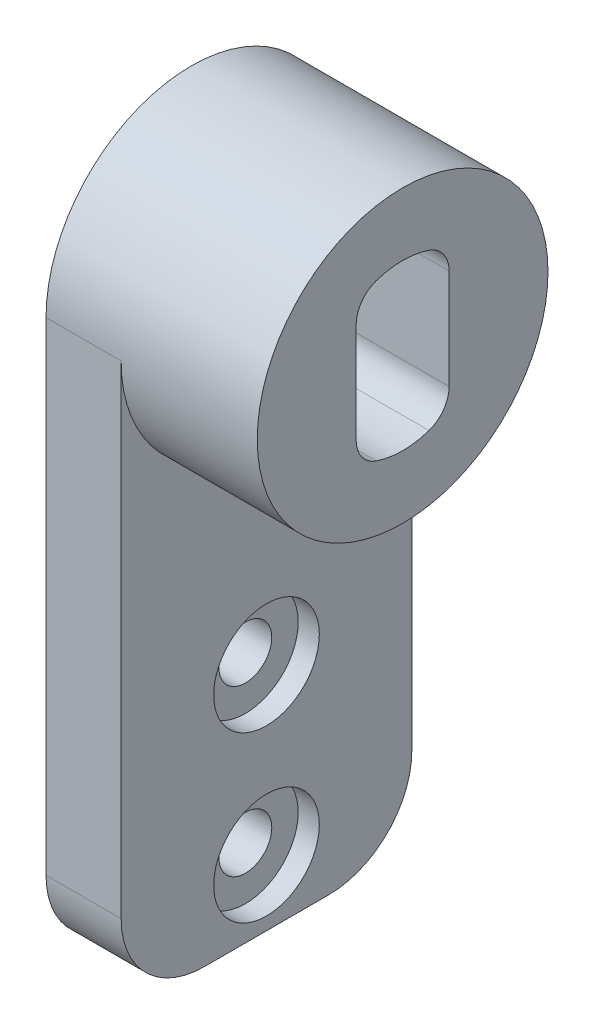
SolidWorks part; units mm, degrees
material "ABS"
ref_plane "Front Plane" through (0, 0, 0) normal (1, 0, 0) x (0, 1, 0)
ref_plane "Top Plane" through (0, 0, 0) normal (0, 0, 1) x (0, 1, 0)
ref_plane "Right Plane" through (0, 0, 0) normal (0, 1, 0) x (-1, 0, 0)
sketch "Sketch1" plane through (0, 0, 0) normal (1, 0, 0) x (0, 1, 0)
  circle A2 centre (0, 0) radius 8.7376
  dimension "D3" = 17.4752
extrude "Boss-Extrude1" add sketch "Sketch1" along normal blind 12.7 contours A2 region at (0, 0, 0)
sketch "Sketch10" plane through (0, 0, 0) normal (-1, 0, 0) x (0, -1, 0)
  line L0 (0, 8.7376) -> (34.036, 8.7376)
  line L2 (34.036, 8.7376) -> (34.036, -8.7376)
  line L3 (34.036, -8.7376) -> (0, -8.7376)
  circle A0 centre (0, 0) radius 8.7376 construction
  arc A2 (0, 8.7376) -> (0, -8.7376) centre (0, 0) cw
  dimension "D1" = 34.036
extrude "Boss-Extrude3" add sketch "Sketch10" against normal blind 4.516 contours L0 A2 L3 L2 region at (0, -20.3793, 0)
fillet "Fillet2" radius 5 2 edges at (2.258, -34.036, 8.7376) (2.258, -34.036, -8.7376)
sketch "Sketch14" [suppressed] plane through (0, 0, 0) normal (-1, 0, 0) x (0, 0, 1)
  line L0 (0.5115, -3.4237) -> (0.3944, -4.0089)
  line L1 (0, 0) -> (0, -4.064) construction
  line L2 (0, 0) -> (0.5606, -3.4335) construction
  line L3 (0.6039, -3.4087) -> (0.9011, -3.9262)
  line L4 (-0.6903, -3.3922) -> (-1.0005, -3.9021)
  line L5 (-0.5983, -3.4096) -> (-0.4961, -3.9976)
  line L6 (-1.8089, -2.9515) -> (-2.2748, -3.3245)
  line L7 (-1.7284, -2.9994) -> (-1.8334, -3.5869)
  line L8 (-2.7093, -2.1549) -> (-3.2746, -2.346)
  line L9 (-2.65, -2.2273) -> (-2.9496, -2.7435)
  line L10 (-3.2829, -1.0983) -> (-3.8795, -1.0846)
  line L11 (-3.252, -1.1867) -> (-3.7101, -1.5692)
  line L12 (-3.4605, 0.0907) -> (-4.0165, 0.3077)
  line L13 (-3.4617, -0.0029) -> (-4.023, -0.2057)
  line L14 (-3.2208, 1.2689) -> (-3.669, 1.6629)
  line L15 (-3.2539, 1.1813) -> (-3.8507, 1.1827)
  line L16 (-2.5926, 2.2939) -> (-2.879, 2.8175)
  line L17 (-2.6537, 2.223) -> (-3.214, 2.4284)
  line L18 (-1.6517, 3.0423) -> (-1.7417, 3.6323)
  line L19 (-1.7333, 2.9965) -> (-2.1896, 3.3812)
  line L20 (-0.5115, 3.4237) -> (-0.3944, 4.0089)
  line L21 (-0.6039, 3.4087) -> (-0.9011, 3.9262)
  line L22 (0.6903, 3.3922) -> (1.0005, 3.9021)
  line L23 (0.5983, 3.4096) -> (0.4961, 3.9976)
  line L24 (1.8089, 2.9515) -> (2.2748, 3.3245)
  line L25 (1.7284, 2.9994) -> (1.8334, 3.5869)
  line L26 (2.7093, 2.1549) -> (3.2746, 2.346)
  line L27 (2.65, 2.2273) -> (2.9496, 2.7435)
  line L28 (3.2829, 1.0983) -> (3.8795, 1.0846)
  line L29 (3.252, 1.1867) -> (3.7101, 1.5692)
  line L30 (3.4605, -0.0907) -> (4.0165, -0.3077)
  line L31 (3.4617, 0.0029) -> (4.023, 0.2057)
  line L32 (3.2208, -1.2689) -> (3.669, -1.6629)
  line L33 (3.2539, -1.1813) -> (3.8507, -1.1827)
  line L34 (2.5926, -2.2939) -> (2.879, -2.8175)
  line L35 (2.6537, -2.223) -> (3.214, -2.4284)
  line L36 (1.6517, -3.0423) -> (1.7417, -3.6323)
  line L37 (1.7333, -2.9965) -> (2.1896, -3.3812)
  line L38 (-0.1032, -4.0627) -> (0, -4.064)
  line L39 (-1.4865, -3.7824) -> (-1.39, -3.8189)
  line L40 (-2.6905, -3.0459) -> (-2.6123, -3.1132)
  line L41 (-3.5195, -2.032) -> (-3.57, -1.942)
  line L42 (-4.0023, -0.7057) -> (-4.0189, -0.6039)
  line L43 (-4.0023, 0.7057) -> (-3.9831, 0.8071)
  line L44 (-3.5195, 2.032) -> (-3.4668, 2.1207)
  line L45 (-2.6123, 3.1132) -> (-2.5324, 3.1785)
  line L46 (-1.39, 3.8189) -> (-1.2926, 3.853)
  line L47 (0, 4.064) -> (0.1032, 4.0627)
  line L48 (1.39, 3.8189) -> (1.4865, 3.7824)
  line L49 (2.6123, 3.1132) -> (2.6905, 3.0459)
  line L50 (3.5195, 2.032) -> (3.57, 1.942)
  line L51 (4.0023, 0.7057) -> (4.0189, 0.6039)
  line L52 (4.0023, -0.7057) -> (3.9831, -0.8071)
  line L53 (3.5195, -2.032) -> (3.4668, -2.1207)
  line L54 (2.6123, -3.1132) -> (2.5324, -3.1785)
  line L55 (1.39, -3.8189) -> (1.2926, -3.853)
  arc A0 (0.3497, -4.0489) -> (0, -4.064) centre (0, 0) cw
  arc A1 (0.3497, -4.0489) -> (0.3944, -4.0089) centre (0.3454, -3.9991) ccw
  arc A2 (0.5115, -3.4237) -> (0.6039, -3.4087) centre (0.5606, -3.4335) cw
  arc A3 (0.4203, -4.0631) -> (0.3944, -4.0089) centre (0.4434, -4.0187) cw
  arc A4 (0.4203, -4.0631) -> (0.7372, -4.2116) centre (2.3016, -0.4608) ccw
  arc A6 (0.9562, -3.9499) -> (0.9011, -3.9262) centre (0.9445, -3.9013) cw
  arc A7 (0.9562, -3.9499) -> (1.2926, -3.853) centre (0, 0) ccw
  arc A8 (-1.0562, -3.9243) -> (-1.39, -3.8189) centre (0, 0) cw
  arc A9 (-1.0562, -3.9243) -> (-1.0005, -3.9021) centre (-1.0432, -3.8761) ccw
  arc A10 (-0.6903, -3.3922) -> (-0.5983, -3.4096) centre (-0.6476, -3.4182) cw
  arc A11 (-0.4524, -4.0387) -> (-0.4961, -3.9976) centre (-0.4468, -3.9891) cw
  arc A12 (-0.4524, -4.0387) -> (-0.1032, -4.0627) centre (0, 0) ccw
  arc A13 (-2.3347, -3.3264) -> (-2.6123, -3.1132) centre (0, 0) cw
  arc A14 (-2.3347, -3.3264) -> (-2.2748, -3.3245) centre (-2.306, -3.2855) ccw
  arc A15 (-1.8089, -2.9515) -> (-1.7284, -2.9994) centre (-1.7776, -2.9906) cw
  arc A16 (-1.8064, -3.6405) -> (-1.8334, -3.5869) centre (-1.7842, -3.5957) cw
  arc A17 (-1.8064, -3.6405) -> (-1.4865, -3.7824) centre (0, 0) ccw
  arc A18 (-3.3316, -2.3273) -> (-3.5195, -2.032) centre (0, 0) cw
  arc A19 (-3.3316, -2.3273) -> (-3.2746, -2.346) centre (-3.2906, -2.2987) ccw
  arc A20 (-2.7093, -2.1549) -> (-2.65, -2.2273) centre (-2.6933, -2.2022) cw
  arc A21 (-2.9426, -2.8031) -> (-2.9496, -2.7435) centre (-2.9064, -2.7686) cw
  arc A22 (-2.9426, -2.8031) -> (-2.6905, -3.0459) centre (0, 0) ccw
  arc A23 (-3.9267, -1.0475) -> (-4.0023, -0.7057) centre (0, 0) cw
  arc A24 (-3.9267, -1.0475) -> (-3.8795, -1.0846) centre (-3.8784, -1.0346) ccw
  arc A25 (-3.2829, -1.0983) -> (-3.252, -1.1867) centre (-3.284, -1.1483) cw
  arc A26 (-3.7238, -1.6276) -> (-3.7101, -1.5692) centre (-3.678, -1.6076) cw
  arc A27 (-3.7238, -1.6276) -> (-3.57, -1.942) centre (0, 0) ccw
  arc A28 (-4.0481, 0.3587) -> (-4.0023, 0.7057) centre (0, 0) cw
  arc A29 (-4.0481, 0.3587) -> (-4.0165, 0.3077) centre (-3.9983, 0.3543) ccw
  arc A30 (-3.4605, 0.0907) -> (-3.4617, -0.0029) centre (-3.4787, 0.0442) cw
  arc A31 (-4.0559, -0.2558) -> (-4.023, -0.2057) centre (-4.006, -0.2527) cw
  arc A32 (-4.0559, -0.2558) -> (-4.0189, -0.6039) centre (0, 0) ccw
  arc A33 (-3.6813, 1.7216) -> (-3.5195, 2.032) centre (0, 0) cw
  arc A34 (-3.6813, 1.7216) -> (-3.669, 1.6629) centre (-3.636, 1.7005) ccw
  arc A35 (-3.2208, 1.2689) -> (-3.2539, 1.1813) centre (-3.2538, 1.2313) cw
  arc A36 (-3.8988, 1.1468) -> (-3.8507, 1.1827) centre (-3.8509, 1.1327) cw
  arc A37 (-3.8988, 1.1468) -> (-3.9831, 0.8071) centre (0, 0) ccw
  arc A38 (-2.8705, 2.8769) -> (-2.6123, 3.1132) centre (0, 0) cw
  arc A39 (-2.8705, 2.8769) -> (-2.879, 2.8175) centre (-2.8352, 2.8415) ccw
  arc A40 (-2.5926, 2.2939) -> (-2.6537, 2.223) centre (-2.6365, 2.2699) cw
  arc A41 (-3.2715, 2.4111) -> (-3.214, 2.4284) centre (-3.2312, 2.3815) cw
  arc A42 (-3.2715, 2.4111) -> (-3.4668, 2.1207) centre (0, 0) ccw
  arc A43 (-1.7134, 3.6852) -> (-1.39, 3.8189) centre (0, 0) cw
  arc A44 (-1.7134, 3.6852) -> (-1.7417, 3.6323) centre (-1.6923, 3.6398) ccw
  arc A45 (-1.6517, 3.0423) -> (-1.7333, 2.9965) centre (-1.7011, 3.0348) cw
  arc A46 (-2.2495, 3.3846) -> (-2.1896, 3.3812) centre (-2.2218, 3.343) cw
  arc A47 (-2.2495, 3.3846) -> (-2.5324, 3.1785) centre (0, 0) ccw
  arc A48 (-0.3497, 4.0489) -> (0, 4.064) centre (0, 0) cw
  arc A49 (-0.3497, 4.0489) -> (-0.3944, 4.0089) centre (-0.3454, 3.9991) ccw
  arc A50 (-0.5115, 3.4237) -> (-0.6039, 3.4087) centre (-0.5606, 3.4335) cw
  arc A51 (-0.9562, 3.9499) -> (-0.9011, 3.9262) centre (-0.9445, 3.9013) cw
  arc A52 (-0.9562, 3.9499) -> (-1.2926, 3.853) centre (0, 0) ccw
  arc A53 (1.0562, 3.9243) -> (1.39, 3.8189) centre (0, 0) cw
  arc A54 (1.0562, 3.9243) -> (1.0005, 3.9021) centre (1.0432, 3.8761) ccw
  arc A55 (0.6903, 3.3922) -> (0.5983, 3.4096) centre (0.6476, 3.4182) cw
  arc A56 (0.4524, 4.0387) -> (0.4961, 3.9976) centre (0.4468, 3.9891) cw
  arc A57 (0.4524, 4.0387) -> (0.1032, 4.0627) centre (0, 0) ccw
  arc A58 (2.3347, 3.3264) -> (2.6123, 3.1132) centre (0, 0) cw
  arc A59 (2.3347, 3.3264) -> (2.2748, 3.3245) centre (2.306, 3.2855) ccw
  arc A60 (1.8089, 2.9515) -> (1.7284, 2.9994) centre (1.7776, 2.9906) cw
  arc A61 (1.8064, 3.6405) -> (1.8334, 3.5869) centre (1.7842, 3.5957) cw
  arc A62 (1.8064, 3.6405) -> (1.4865, 3.7824) centre (0, 0) ccw
  arc A63 (3.3316, 2.3273) -> (3.5195, 2.032) centre (0, 0) cw
  arc A64 (3.3316, 2.3273) -> (3.2746, 2.346) centre (3.2906, 2.2987) ccw
  arc A65 (2.7093, 2.1549) -> (2.65, 2.2273) centre (2.6933, 2.2022) cw
  arc A66 (2.9426, 2.8031) -> (2.9496, 2.7435) centre (2.9064, 2.7686) cw
  arc A67 (2.9426, 2.8031) -> (2.6905, 3.0459) centre (0, 0) ccw
  arc A68 (3.9267, 1.0475) -> (4.0023, 0.7057) centre (0, 0) cw
  arc A69 (3.9267, 1.0475) -> (3.8795, 1.0846) centre (3.8784, 1.0346) ccw
  arc A70 (3.2829, 1.0983) -> (3.252, 1.1867) centre (3.284, 1.1483) cw
  arc A71 (3.7238, 1.6276) -> (3.7101, 1.5692) centre (3.678, 1.6076) cw
  arc A72 (3.7238, 1.6276) -> (3.57, 1.942) centre (0, 0) ccw
  arc A73 (4.0481, -0.3587) -> (4.0023, -0.7057) centre (0, 0) cw
  arc A74 (4.0481, -0.3587) -> (4.0165, -0.3077) centre (3.9983, -0.3543) ccw
  arc A75 (3.4605, -0.0907) -> (3.4617, 0.0029) centre (3.4787, -0.0442) cw
  arc A76 (4.0559, 0.2558) -> (4.023, 0.2057) centre (4.006, 0.2527) cw
  arc A77 (4.0559, 0.2558) -> (4.0189, 0.6039) centre (0, 0) ccw
  arc A78 (3.6813, -1.7216) -> (3.5195, -2.032) centre (0, 0) cw
  arc A79 (3.6813, -1.7216) -> (3.669, -1.6629) centre (3.636, -1.7005) ccw
  arc A80 (3.2208, -1.2689) -> (3.2539, -1.1813) centre (3.2538, -1.2313) cw
  arc A81 (3.8988, -1.1468) -> (3.8507, -1.1827) centre (3.8509, -1.1327) cw
  arc A82 (3.8988, -1.1468) -> (3.9831, -0.8071) centre (0, 0) ccw
  arc A83 (2.8705, -2.8769) -> (2.6123, -3.1132) centre (0, 0) cw
  arc A84 (2.8705, -2.8769) -> (2.879, -2.8175) centre (2.8352, -2.8415) ccw
  arc A85 (2.5926, -2.2939) -> (2.6537, -2.223) centre (2.6365, -2.2699) cw
  arc A86 (3.2715, -2.4111) -> (3.214, -2.4284) centre (3.2312, -2.3815) cw
  arc A87 (3.2715, -2.4111) -> (3.4668, -2.1207) centre (0, 0) ccw
  arc A88 (1.7134, -3.6852) -> (1.39, -3.8189) centre (0, 0) cw
  arc A89 (1.7134, -3.6852) -> (1.7417, -3.6323) centre (1.6923, -3.6398) ccw
  arc A90 (1.6517, -3.0423) -> (1.7333, -2.9965) centre (1.7011, -3.0348) cw
  arc A91 (2.2495, -3.3846) -> (2.1896, -3.3812) centre (2.2218, -3.343) cw
  arc A92 (2.2495, -3.3846) -> (2.5324, -3.1785) centre (0, 0) ccw
  point P207 (0, 0)
  dimension "D1" = 4.064
  dimension "D2" = 0.05
  dimension "D3" = 0.05
  dimension "D4" = 0.04
  dimension "D5" = 18
  dimension "D6" = 0.5968
  dimension "D8" = 0.35
sketch "Sketch22" plane through (12.7, 0, 0) normal (1, 0, 0) x (0, 1, 0)
  line L7 (-4.0897, -2.794) -> (4.0897, 2.794) construction
  line L8 (-4.0897, 2.794) -> (4.0897, -2.794) construction
  line L11 (-4.0897, -2.794) -> (4.0897, -2.794)
  line L13 (-4.0897, 2.794) -> (4.0897, 2.794)
  line L15 (-4.0897, -2.794) -> (4.0897, 2.794) construction
  line L16 (-4.0897, 2.794) -> (4.0897, -2.794) construction
  arc A3 (-4.0897, 2.794) -> (-4.0897, -2.794) centre (0, 0) ccw
  arc A4 (4.0897, -2.794) -> (4.0897, 2.794) centre (0, 0) ccw
  dimension "D2" = 9.906
  dimension "D3" = 5.588
extrude "Cut-Extrude10" cut sketch "Sketch22" against normal blind 12.192
sketch "Sketch23" plane through (0, 0, 0) normal (-1, 0, 0) x (0, 0, 1)
  line L0 (0, -33.5187) -> (0, 0) construction
  line L2 (0, -30.0897) -> (0, -20.1843) construction
  line L3 (0, -20.1843) -> (0, -10.279) construction
  line L6 (-3.7376, -33.5187) -> (3.7376, -33.5187)
  line L7 (8.2296, -29.0267) -> (8.2296, 0)
  line L8 (-8.2296, 0) -> (-8.2296, -29.0267)
  arc A6 (-8.2296, -29.0267) -> (-3.7376, -33.5187) centre (-3.7376, -29.0267) ccw
  arc A7 (3.7376, -33.5187) -> (8.2296, -29.0267) centre (3.7376, -29.0267) ccw
  arc A8 (8.2296, 0) -> (-8.2296, 0) centre (0, 0) ccw
  circle A9 centre (0, -30.0897) radius 1.5875
  circle A10 centre (0, -20.1843) radius 1.5875
  dimension "D1" = 3.175
  dimension "D3" = 4.492
  dimension "D5" = 8.2296
  dimension "D2" = 9.9054
  dimension "D4" = 29.0267
  dimension "D6" = 3.429
extrude "Cut-Extrude11" cut sketch "Sketch23" against normal through all contours A10 | A9 region at (0, -30.0897, 0) region at (0, -20.1843, 0)
sketch "Sketch24" plane through (4.516, 0, 0) normal (1, 0, 0) x (0, 1, 0)
  circle A0 centre (-20.1843, 0) radius 1.5875 construction
  circle A1 centre (-20.1843, 0) radius 1.5875
  circle A2 centre (-20.1843, 0) radius 3.175
  circle A3 centre (-30.0897, 0) radius 3.175
  dimension "D1" = 6.35
  dimension "D2" = 6.35
extrude "Cut-Extrude13" cut sketch "Sketch24" against normal blind 1.27
fillet "Fillet11" radius 1.778 4 edges at (6.604, 4.0897, -2.794) (6.604, 4.0897, 2.794) (6.604, -4.0897, -2.794) (6.604, -4.0897, 2.794)
